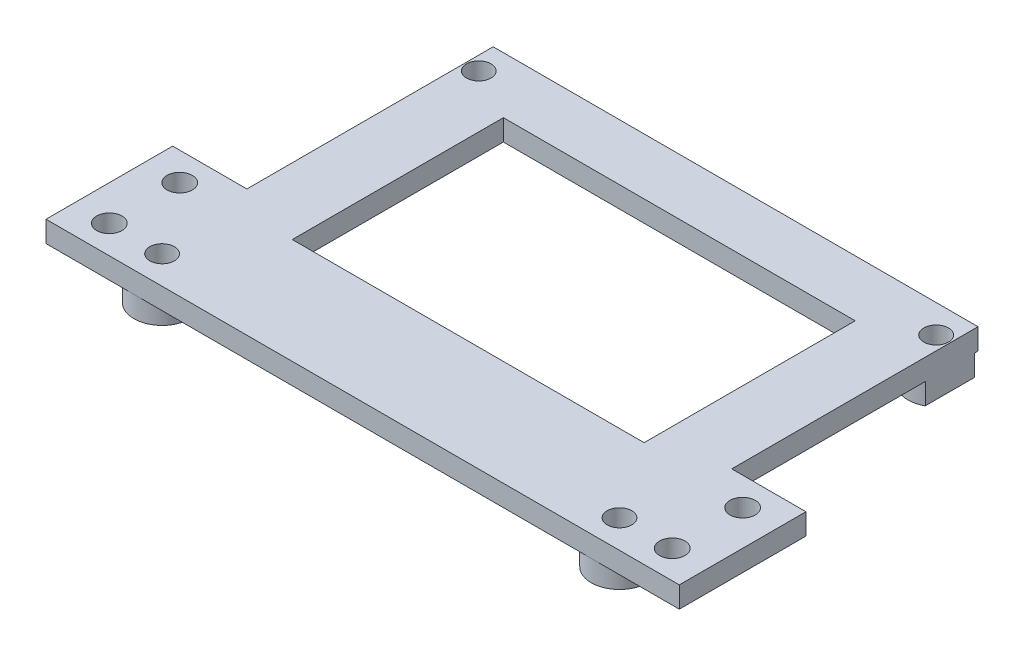
SolidWorks part; units mm, degrees
ref_plane "Front Plane" through (0, 0, 0) normal (0, 0, 1) x (1, 0, 0)
ref_plane "Top Plane" through (0, 0, 0) normal (0, 1, 0) x (1, 0, 0)
ref_plane "Right Plane" through (0, 0, 0) normal (1, 0, 0) x (0, 0, -1)
sketch "Sketch1" plane through (0, 0, 0) normal (0, 1, 0) x (1, 0, 0)
  line L1 (34.85, -9) -> (-34.85, -9)
  line L2 (34.85, -9) -> (34.85, 9)
  line L3 (34.85, 9) -> (-34.85, 9)
  line L4 (-34.85, -9) -> (-34.85, 9)
  line L5 (34.85, -9) -> (-34.85, 9) construction
  line L6 (34.85, 9) -> (-34.85, -9) construction
  line L7 (45, -9) -> (-45, -9)
  line L8 (45, -9) -> (45, 9)
  line L9 (45, 9) -> (-45, 9)
  line L10 (-45, -9) -> (-45, 9)
  line L11 (45, -9) -> (-45, 9) construction
  line L12 (45, 9) -> (-45, -9) construction
  point P0 (0, 0)
  point P6 (0, 0)
  dimension "D1" = 69.7
  dimension "D2" = 90
  dimension "D3" = 18
extrude "Boss-Extrude1" add sketch "Sketch1" along normal blind 3 contours L10 L7 L4 L9 | L4 L1 L2 L3 | L8 L9 L2 L7 region at (0, 0, 0) region at (39.925, 0, 0) region at (-39.925, 0, 0)
extrude "Boss-Extrude2" add sketch "Sketch1<3>" along normal blind 8 contours L4 L1 L2 L3 region at (0, 0, 0)
sketch "Sketch1<3>" plane through (0, 0, 0) normal (0, 1, 0) x (1, 0, 0) same geometry as "Sketch1"
sketch "Sketch4" plane through (0, 3, 0) normal (0, 1, 0) x (1, 0, 0)
  line L0 (-45, -9) -> (-45, 9) construction
  line L1 (45, -9) -> (45, 9) construction
  line L2 (45, 9) -> (34.85, 9) construction
  line L3 (-34.85, 9) -> (-45, 9) construction
  line L4 (-34.85, -9) -> (-45, -9) construction
  line L5 (45, -9) -> (34.85, -9) construction
  point P0 (-40, 5)
  point P2 (-40, -5)
  point P4 (40, -5)
  point P6 (40, 5)
  dimension "D1" = 5
  dimension "D2" = 5
  dimension "D3" = 4
  dimension "D4" = 4
  dimension "D5" = 4
  dimension "D6" = 4
hole_wizard "M3 Clearance Hole1" positions "Sketch4" profile "Sketch5" hole size "M3" standard "ANSI Metric"
sketch "Sketch5" plane through (-40, 3, -5) normal (1, 0, 0) x (0, 0, 1)
  line L0 (0, 0) -> (0, 11.0815)
  line L1 (0, 11.0815) -> (1.8, 10)
  line L2 (1.8, 10) -> (1.8, 0)
  line L5 (1.8, 0) -> (0, 0)
  line L10 (0, 11.0815) -> (-1.8, 10) construction
  line L11 (0, -6.35) -> (0, 107.95) construction
  dimension "Hole Dia." = 3.6
  dimension "Hole Depth" = 10
  dimension "Drill Angle" = 118
sketch "Sketch6" plane through (0, 0, 0) normal (0, -1, 0) x (1, 0, 0)
  line L1 (34.85, 9) -> (-34.85, 9)
  line L2 (34.85, 9) -> (34.85, -46)
  line L3 (34.85, -46) -> (-34.85, -46)
  line L4 (-34.85, 9) -> (-34.85, -9)
  line L5 (34.85, 9) -> (-34.85, 9)
  line L6 (34.85, -9) -> (34.85, 9)
  line L7 (-34.85, -9) -> (34.85, -9)
  line L8 (-34.85, 9) -> (-34.85, -9)
  line L9 (34.85, 9) -> (-34.85, 9)
  line L10 (34.85, -9) -> (34.85, 9)
  line L11 (-34.85, -9) -> (34.85, -9)
  line L12 (-34.85, 9) -> (-34.85, -46)
  line M12 (-45, -9) -> (45, -9)
  dimension "D2" = 55
  dimension "D1" = 0
extrude "Boss-Extrude3" add sketch "Sketch6" against normal blind 5 contours L12 L3 L2 M12 region at (0, 0, -27.5)
sketch "Sketch9" plane through (0, 0, 0) normal (0, -1, 0) x (1, 0, 0)
  line L0 (45, 9) -> (-45, 9) construction
  line L1 (32.5, 5) -> (-32.5, 5)
  line L2 (32.5, 5) -> (32.5, -40)
  line L3 (32.5, -40) -> (-32.5, -40)
  line L4 (-32.5, 5) -> (-32.5, -40)
  line L5 (32.5, 5) -> (-32.5, -40) construction
  line L6 (32.5, -40) -> (-32.5, 5) construction
  line L15 (-45, 9) -> (-45, -9)
  line L16 (-45, -9) -> (-34.85, -9)
  line L17 (-34.85, -9) -> (-34.85, -46)
  line L18 (-34.85, -46) -> (34.85, -46)
  line L19 (34.85, -46) -> (34.85, -9)
  line L20 (34.85, -9) -> (45, -9)
  line L21 (45, -9) -> (45, 9)
  line L22 (45, 9) -> (-45, 9)
  line L23 (-45, 9) -> (-45, -9)
  line L24 (-45, -9) -> (-34.85, -9)
  line L25 (-34.85, -9) -> (-34.85, -46)
  line L26 (-34.85, -46) -> (34.85, -46)
  line L27 (34.85, -46) -> (34.85, -9)
  line L28 (34.85, -9) -> (45, -9)
  line L29 (45, -9) -> (45, 9)
  line L30 (45, 9) -> (-45, 9)
  circle A0 centre (32.5, -40) radius 4
  circle A1 centre (-32.5, -40) radius 4
  circle A2 centre (-32.5, 5) radius 4
  circle A3 centre (32.5, 5) radius 4
  point P0 (0, -17.5)
  point P8 (0, 9)
  dimension "D4" = 8
  dimension "D1" = 65
  dimension "D2" = 45
  dimension "D3" = 4
  dimension "D5" = 0
extrude "Boss-Extrude4" add sketch "Sketch9" along normal blind 3 contours L27 A0 L2 L3 | L2 A0 L3 | L4 A1 L25 L3 | L3 A1 L4 | L4 A2 L1 | L1 A2 L4 | L2 A3 L1 | L1 A3 L2 region at (-30.8023, 0, 3.3023) region at (-33.0659, 0, 5.5659) region at (33.0659, 0, 5.5659) region at (30.8023, 0, 3.3023) region at (-30.8023, 0, -38.3023) region at (-32.4578, 0, -40.7059) region at (32.4578, 0, -40.7059) region at (30.8023, 0, -38.3023)
sketch "Sketch10" plane through (0, -3, 0) normal (0, -1, 0) x (-1, 0, 0)
  circle A2 centre (-32.5, -5) radius 4
  circle A3 centre (-32.5, -5) radius 4
  circle A4 centre (32.5, -5) radius 4 construction
  arc A5 (34.85, 43.2369) -> (34.85, 36.7631) centre (32.5, 40) ccw construction
  arc A6 (-34.85, 36.7631) -> (-34.85, 43.2369) centre (-32.5, 40) ccw construction
  circle A7 centre (32.5, -5) radius 4
  arc A8 (34.85, 43.2369) -> (34.85, 36.7631) centre (32.5, 40) ccw
  arc A9 (-34.85, 36.7631) -> (-34.85, 43.2369) centre (-32.5, 40) ccw
  point P5 (-32.5, -5)
  point P8 (32.5, -5)
  point P10 (32.5, 40)
  point P13 (-32.5, 40)
  dimension "D1" = 0
hole_wizard "Ø3.0mm Dowel Hole1" positions "Sketch10" profile "Sketch11" hole size "Ø3.0" standard "ANSI Metric"
sketch "Sketch11" plane through (32.5, -3, 5) normal (1, 0, 0) x (0, 0, -1)
  line L0 (0, 0) -> (0, 7.0515)
  line L1 (0, 7.0515) -> (1.75, 6)
  line L2 (1.75, 6) -> (1.75, 0)
  line L5 (1.75, 0) -> (0, 0)
  line L10 (0, 7.0515) -> (-1.75, 6) construction
  line L11 (0, -6.35) -> (0, 107.95) construction
  dimension "Hole Dia." = 3.5
  dimension "Hole Depth" = 6
  dimension "Drill Angle" = 118
sketch "Sketch12" plane through (0, 0, 0) normal (0, -1, 0) x (1, 0, 0)
  line L36 (32.5, 9) -> (-32.5, 9) construction
  line L37 (-25, -6) -> (25, -6)
  line L38 (-25, -6) -> (-25, -36)
  line L39 (-25, -36) -> (25, -36)
  line L40 (25, -6) -> (25, -36)
  line L41 (-25, -6) -> (25, -36) construction
  line L42 (-25, -36) -> (25, -6) construction
  line L43 (34.85, -46) -> (-34.85, -46) construction
  point P0 (0, 0)
  point P3 (0, 9)
  point P34 (0, -21)
  dimension "D1" = 30
  dimension "D2" = 50
  dimension "D3" = 10
extrude "Cut-Extrude1" cut sketch "Sketch12" against normal through all
ref_plane "Plane1" through (-34.85, 8, -9) normal (0, 0, -1) x (-1, 0, 0)
sketch "Sketch14" plane through (-34.85, 0, 0) normal (-1, 0, 0) x (0, 0, 1)
  line L1 (9, 8) -> (-46, 8)
  line L2 (9, 8) -> (9, 3)
  line L3 (9, 3) -> (-46, 3)
  line L4 (-46, 8) -> (-46, 3)
  line L12 (-9, 8) -> (-9, 5)
  line L13 (-9, 5) -> (-46, 5)
  line L14 (-46, 5) -> (-46, 0)
  line L15 (-46, 0) -> (-43.2369, 0)
  line L16 (-43.2369, 0) -> (-43.2369, -3)
  line L17 (-43.2369, -3) -> (-36.7631, -3)
  line L18 (-36.7631, -3) -> (-36.7631, 0)
  line L19 (-36.7631, 0) -> (-9, 0)
  line L20 (-9, 0) -> (-9, 3)
  line L21 (-9, 3) -> (9, 3)
  line L22 (9, 3) -> (9, 8)
  line L23 (9, 8) -> (-9, 8)
  line L24 (-9, 8) -> (-9, 5)
  line L25 (-9, 5) -> (-46, 5)
  line L26 (-46, 5) -> (-46, 0)
  line L27 (-46, 0) -> (-43.2369, 0)
  line L28 (-43.2369, 0) -> (-43.2369, -3)
  line L29 (-43.2369, -3) -> (-36.7631, -3)
  line L30 (-36.7631, -3) -> (-36.7631, 0)
  line L31 (-36.7631, 0) -> (-9, 0)
  line L32 (-9, 0) -> (-9, 3)
  line L33 (-9, 3) -> (9, 3)
  line L34 (9, 3) -> (9, 8)
  line L35 (9, 8) -> (-9, 8)
  line M13 (-9, 8) -> (-9, 5)
  line M14 (-9, 5) -> (-46, 5)
  line M15 (-46, 5) -> (-46, 0)
  line M22 (-9, 3) -> (9, 3)
  line M23 (9, 3) -> (9, 8)
  line M24 (9, 8) -> (-9, 8)
  dimension "D1" = 0
extrude "Cut-Extrude2" cut sketch "Sketch14" against normal through all contours L3 M22 M23 M24 M13 M14 M15 region at (-34.85, 4.8232, -12.4085)
sketch "Sketch15" plane through (0, 0, -46) normal (0, 0, -1) x (-1, 0, 0)
  line L4 (34.85, 3) -> (-34.85, 3)
  line L5 (-34.85, 3) -> (-34.85, 0)
  line L6 (-34.85, 0) -> (34.85, 0)
  line L7 (34.85, 0) -> (34.85, 3)
  line L8 (34.85, 3) -> (-34.85, 3)
  line L9 (-34.85, 3) -> (-34.85, 0)
  line L10 (-34.85, 0) -> (34.85, 0)
  line L11 (34.85, 0) -> (34.85, 3)
  dimension "D1" = 0
extrude "Cut-Extrude3" cut sketch "Sketch15" against normal blind 2
sketch "Sketch16" plane through (34.85, 0, 0) normal (1, 0, 0) x (0, 0, -1)
  line L1 (44, 3) -> (9, 3)
  line L2 (44, 3) -> (44, -5.2364)
  line L3 (44, -5.2364) -> (9, -5.2364)
  line L4 (9, 3) -> (9, -5.2364)
  line L8 (44, 0) -> (44, 3)
  line L9 (44, 3) -> (9, 3)
  line L10 (9, 3) -> (9, 0)
  line L11 (9, 0) -> (36.7631, 0)
  line L12 (36.7631, 0) -> (36.7631, -3)
  line L13 (36.7631, -3) -> (43.2369, -3)
  line L14 (43.2369, -3) -> (43.2369, 0)
  line L15 (43.2369, 0) -> (44, 0)
  line L16 (44, 0) -> (44, 3)
  line L17 (44, 3) -> (9, 3)
  line L18 (9, 3) -> (9, 0)
  line L19 (9, 0) -> (36.7631, 0)
  line L20 (36.7631, 0) -> (36.7631, -3)
  line L21 (36.7631, -3) -> (43.2369, -3)
  line L22 (43.2369, -3) -> (43.2369, 0)
  line L23 (43.2369, 0) -> (44, 0)
  line M9 (44, 0) -> (44, 3)
  line M10 (44, 3) -> (9, 3)
  line M11 (9, 3) -> (9, 0)
  line M12 (9, 0) -> (36.7631, 0)
  line M13 (36.7631, 0) -> (36.7631, -3)
  line M14 (36.7631, -3) -> (43.2369, -3)
  line M15 (43.2369, -3) -> (43.2369, 0)
  line M16 (43.2369, 0) -> (44, 0)
  dimension "D1" = 0
extrude "Cut-Extrude4" cut sketch "Sketch16" against normal blind 0.4 contours M16 M9 M10 M11 M12 M13 M14 M15 | L4 L3 L2 M12 M16 M15 M14 M13 region at (34.85, 1.0317, -28.6073) region at (34.85, -2.7507, -24.8998)
mirror "Mirror1" about plane through (0, 0, 0) normal (1, 0, 0) of "Cut-Extrude4"
